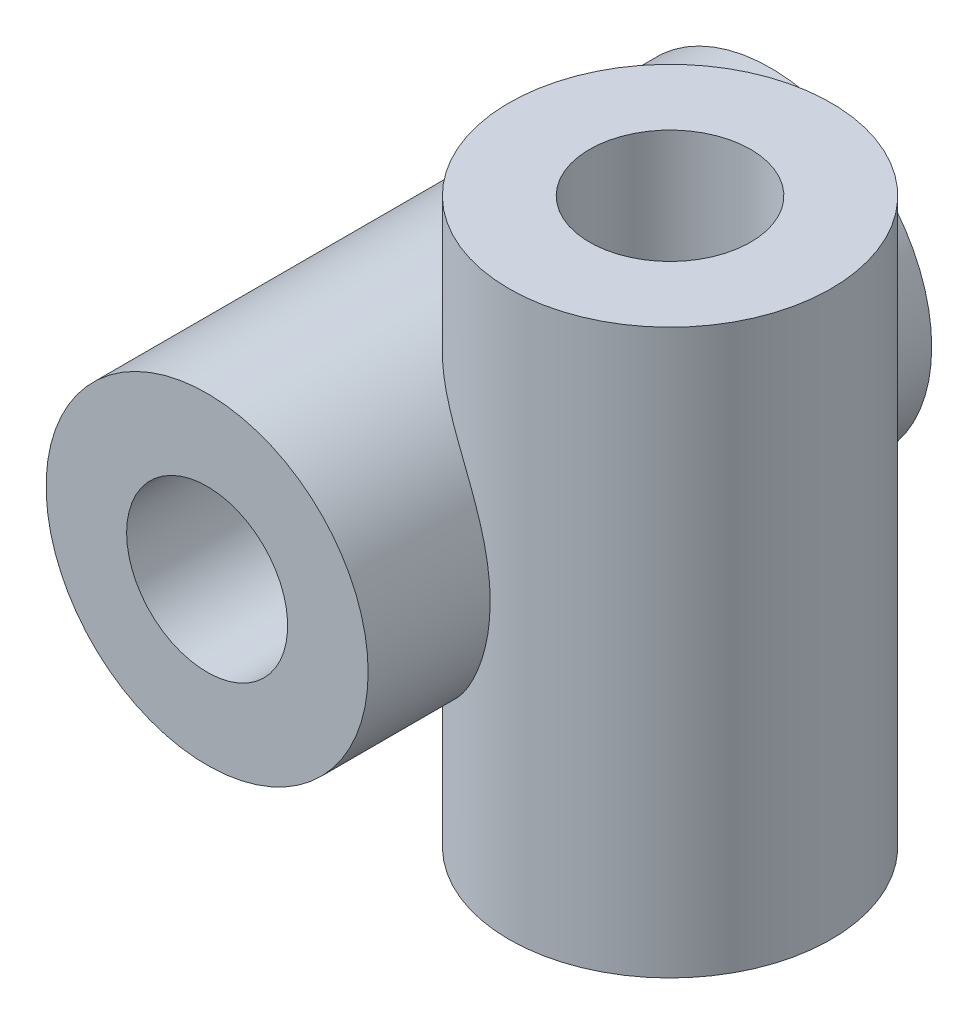
SolidWorks part; units mm, degrees
ref_plane "Front Plane" through (0, 0, 0) normal (0, 0, 1) x (1, 0, 0)
ref_plane "Top Plane" through (0, 0, 0) normal (0, 1, 0) x (1, 0, 0)
ref_plane "Right Plane" through (0, 0, 0) normal (1, 0, 0) x (0, 0, -1)
sketch "Sketch1" plane through (0, 0, 0) normal (0, 0, 1) x (1, 0, 0)
  circle A0 centre (0, 0) radius 8
  circle A1 centre (0, 0) radius 16
  dimension "D1" = 16
  dimension "D2" = 32
extrude "Boss-Extrude1" add sketch "Sketch1" along normal blind 56
sketch "Sketch2" plane through (0, 0, 0) normal (0, 1, 0) x (1, 0, 0)
  line L0 (16, 0) -> (-16, 0) construction
  line L1 (16, 0) -> (-16, 0)
  line L2 (-16, -56) -> (16, -56) construction
  line L3 (-16, 0) -> (-16, -56) construction
  line L4 (16, -56) -> (16, 0) construction
  line L5 (-16, -56) -> (16, -56)
  line L6 (-16, 0) -> (-16, -56)
  line L7 (16, -56) -> (16, 0)
  line L8 (0, 0) -> (0, -56) construction
  line L10 (16, -28) -> (-16, -28) construction
  circle A0 centre (18, -28) radius 8
  circle A1 centre (18, -28) radius 16
  dimension "D1" = 32
  dimension "D2" = 16
  dimension "D3" = 18
extrude "Boss-Extrude2" add sketch "Sketch2" along normal mid plane 56 contours L7 A1 A0 | L7 A1 A0 region at (28.3402, 0, 16.2754) region at (9.2514, 0, 28)
sketch "Sketch3" plane through (0, 0, 0) normal (0, 0, -1) x (-1, 0, 0)
  circle A0 centre (0, 0) radius 8 construction
  circle A1 centre (0, 0) radius 8
extrude "Cut-Extrude1" cut sketch "Sketch3" against normal through all
sketch "Sketch4" plane through (0, -28, 0) normal (0, -1, 0) x (1, 0, 0)
  circle A0 centre (18, 28) radius 8 construction
  circle A1 centre (18, 28) radius 8
extrude "Cut-Extrude2" cut sketch "Sketch4" against normal through all
